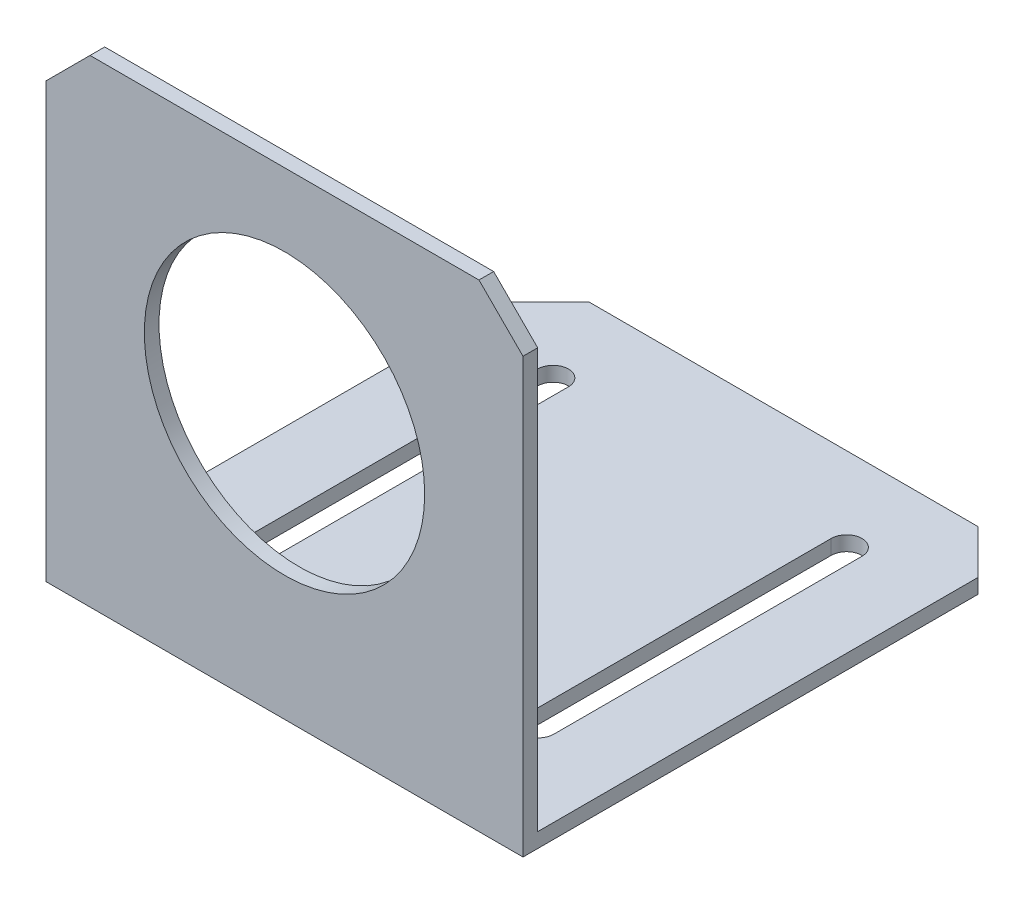
SolidWorks part; units mm, degrees
ref_plane "前视基准面" through (0, 0, 0) normal (0, 0, 1) x (1, 0, 0)
ref_plane "上视基准面" through (0, 0, 0) normal (0, 1, 0) x (1, 0, 0)
ref_plane "右视基准面" through (0, 0, 0) normal (1, 0, 0) x (0, 0, -1)
sketch "草图1" plane through (0, 0, 0) normal (0, 0, 1) x (1, 0, 0)
  line L1 (-28.9531, 47.6797) -> (36.0469, 47.6797)
  line L2 (-28.9531, 47.6797) -> (-28.9531, -17.4203)
  line L3 (-28.9531, -17.4203) -> (36.0469, -17.4203)
  line L4 (36.0469, 47.6797) -> (36.0469, -17.4203)
  circle A0 centre (3.5469, 18.6797) radius 19.1
  dimension "D3" = 38.2
  dimension "D1" = 65.1
  dimension "D2" = 65
  dimension "D5" = 29
extrude "凸台-拉伸1" add sketch "草图1" along normal blind 2
sketch "草图3" plane through (36.0469, 0, 0) normal (1, 0, 0) x (0, 0, -1)
  line L0 (0, -15.4203) -> (66, -15.4203)
  line L2 (66, -15.4203) -> (66, -17.4203)
  line L3 (66, -17.4203) -> (0, -17.4203)
  line L5 (0, -15.4203) -> (0, -17.4203)
  dimension "D1" = 66
extrude "凸台-拉伸2" add sketch "草图3" against normal blind 65
sketch "草图4" plane through (0, -15.4203, 0) normal (0, 1, 0) x (1, 0, 0)
  line L0 (3.5469, 0) -> (3.5469, 66) construction
  line L1 (-28.9531, 0) -> (36.0469, 0) construction
  line L2 (-28.9531, 66) -> (36.0469, 66) construction
  line L3 (23.5469, 12.5947) -> (23.5469, 54.5947) construction
  line L4 (21.4469, 12.5947) -> (21.4469, 54.5947)
  line L5 (25.6469, 12.5947) -> (25.6469, 54.5947)
  line L6 (36.0469, 66) -> (36.0469, 0) construction
  line L7 (-16.4531, 12.5947) -> (-16.4531, 54.5947) construction
  line L8 (-14.3531, 12.5947) -> (-14.3531, 54.5947)
  line L9 (-18.5531, 12.5947) -> (-18.5531, 54.5947)
  arc A0 (21.4469, 12.5947) -> (25.6469, 12.5947) centre (23.5469, 12.5947) ccw
  arc A1 (25.6469, 54.5947) -> (21.4469, 54.5947) centre (23.5469, 54.5947) ccw
  arc A2 (-14.3531, 12.5947) -> (-18.5531, 12.5947) centre (-16.4531, 12.5947) cw
  arc A3 (-18.5531, 54.5947) -> (-14.3531, 54.5947) centre (-16.4531, 54.5947) cw
  point P8 (23.5469, 33.5947)
  point P17 (-16.4531, 33.5947)
  dimension "D1" = 2.1
  dimension "D2" = 42
  dimension "D3" = 12.5
  dimension "D4" = 20
extrude "切除-拉伸2" cut sketch "草图4" against normal through all contours L4 A1 L5 A0 | L9 A3 L8 A2
chamfer "倒角2" distance 6 angle 45 1 edges at (36.0469, -16.4203, -66)
chamfer "倒角3" distance 6 angle 45 1 edges at (-28.9531, -16.4203, -66)
chamfer "倒角4" distance 6 angle 45 1 edges at (-28.9531, 47.6797, 1)
chamfer "倒角5" distance 6 angle 45 1 edges at (36.0469, 47.6797, 1)
